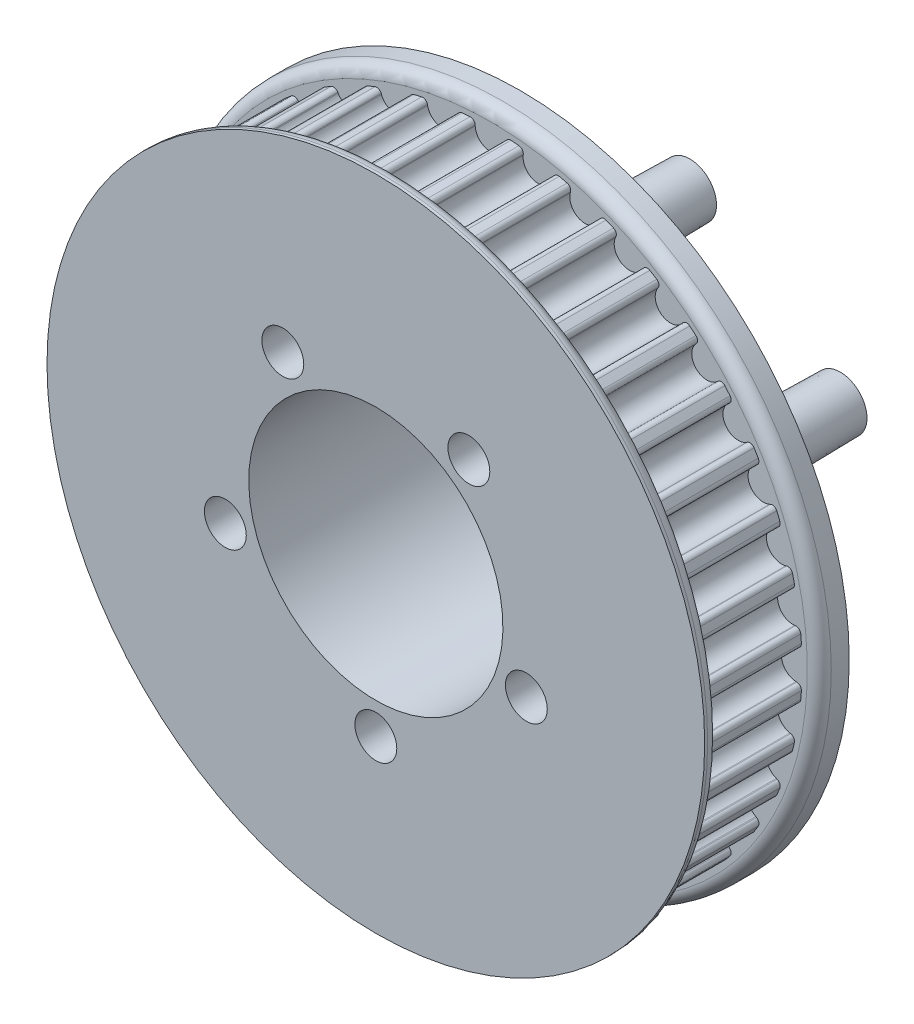
SolidWorks part; units mm, degrees
ref_plane "정면" through (0, 0, 0) normal (0, 0, 1) x (1, 0, 0)
ref_plane "윗면" through (0, 0, 0) normal (0, 1, 0) x (1, 0, 0)
ref_plane "우측면" through (0, 0, 0) normal (1, 0, 0) x (0, 0, -1)
sketch "스케치3" plane through (0, 0, 0) normal (0, 0, 1) x (1, 0, 0)
  line L0 (0, 0) -> (0, 31.2595) construction
  line L1 (0, 0) -> (-4.9795, 31.4391) construction
  line L2 (0, 31.2595) -> (0, 32.9895) construction
  line L3 (-1.5331, 30.6478) -> (-1.5617, 31.2205)
  line L4 (1.5331, 30.6478) -> (1.5617, 31.2205)
  circle A0 centre (0, 0) radius 31.831 construction
  circle A1 centre (0, 0) radius 32.9895 construction
  circle A2 centre (0, 0) radius 31.2595
  circle A3 centre (0, 30.7245) radius 1.535
  dimension "D2" = 63.662
  dimension "D5" = 3.07
  dimension "D3" = 62.519
  dimension "D1" = 9
  dimension "D4" = 2.07
  dimension "D6" = 3.8
extrude "보스-돌출2" add sketch "스케치3" along normal blind 10 contours A2
extrude "컷-돌출2" cut sketch "스케치3<3>" against normal through all and the other way through all contours A3 A2 L3 | A2 A3 | A3 L4 A2 region at (0, 30.3451, 0) region at (-1.5216, 31.0799, 0) region at (1.5216, 31.0799, 0)
sketch "스케치3<3>" plane through (0, 0, 0) normal (0, 0, 1) x (1, 0, 0) same geometry as "스케치3"
fillet "필렛1" radius 0.48 2 edges at (1.5617, 31.2205, 5) (-1.5617, 31.2205, 5)
pattern_circular "원형 패턴1" count 40 over 360 about axis through (0, 0, 10) along (0, 0, -1) of "컷-돌출2", "필렛1"
sketch "스케치8" plane through (0, 0, 10) normal (0, 0, 1) x (1, 0, 0)
  circle A1 centre (0, 0) radius 32.9895 construction
  circle A2 centre (0, 0) radius 32.9895
extrude "보스-돌출3" add sketch "스케치8" along normal blind 1.5
sketch "스케치9" plane through (0, 0, 0) normal (0, 0, -1) x (-1, 0, 0)
  circle A1 centre (0, 0) radius 32.9895 construction
  circle A3 centre (0, 0) radius 32.9895
extrude "보스-돌출4" add sketch "스케치9" along normal blind 3
sketch "스케치7" plane through (0, 0, 0) normal (-1, 0, 0) x (0, 0, 1)
  line L0 (-15.1599, 0) -> (-15.1599, 11)
  line L1 (-15.1599, 0) -> (-1.5048, 0)
  line L3 (-3, 32.9895) -> (-3, -32.9895) construction
  line L5 (-7.7548, 22.06) -> (-7.7548, 0) construction
  line L6 (-1.5048, 0) -> (-1.5048, 34.5)
  line L7 (-0.2048, 26.3473) -> (-5.4, 29.3467)
  line L9 (-7.7548, 22.06) -> (-0.2048, 22.06)
  line L10 (-7.7548, 22.06) -> (-10.6591, 0) construction
  line L13 (-0.2048, 26.3473) -> (-0.2048, 22.06)
  arc A0 (-15.1599, 11) -> (-7.7548, 22.06) centre (-3.198, 11) cw
  arc A1 (-7.7548, 22.06) -> (-1.5048, 34.5) centre (13.2562, 19.2938) cw
  dimension "D1" = 11
  dimension "D2" = 2.4
  dimension "D3" = 6.25
  dimension "D4" = 34.5
  dimension "D5" = 22.06
  dimension "D6" = 7.5
  dimension "D7" = 30
  dimension "D8" = 13.6551
  dimension "D10" = 7.55
  dimension "D11" = 3.8952
revolve "회전2" add sketch "스케치7" angle 360 about L1 region at (0, 10.341, -7.9409) region at (0, 25.0336, -4.3864)
sketch "스케치10" plane through (0, 0, 0) normal (0, 0, 1) x (1, 0, 0)
  line L0 (0, 0) -> (0, 15.875) construction
  circle A0 centre (0, 15.875) radius 2.675
  circle A1 centre (9.3311, 12.8431) radius 2.675 construction
  circle A2 centre (15.098, 4.9056) radius 2.675
  circle A3 centre (15.098, -4.9056) radius 2.675 construction
  circle A4 centre (9.3311, -12.8431) radius 2.675
  circle A5 centre (0, -15.875) radius 2.675 construction
  circle A6 centre (-9.3311, -12.8431) radius 2.675
  circle A7 centre (-15.098, -4.9056) radius 2.675 construction
  circle A8 centre (-15.098, 4.9056) radius 2.675
  circle A9 centre (-9.3311, 12.8431) radius 2.675 construction
  point P25 (0, 0)
  dimension "D1" = 5.35
  dimension "D2" = 15.875
  dimension "D3" = 10
extrude "보스-돌출5" add sketch "스케치10" against normal blind 20
hole_wizard "M5x0.8 탭을 위한 탭 드릴2" positions "스케치14" profile "스케치15" hole size "M5x0.8" standard "Ansi Metric" end condition through all
sketch "스케치14" plane through (0, 0, 11.5) normal (0, 0, -1) x (-1, 0, 0)
  point P26 (-15.098, -4.9056)
  point P28 (0, -15.875)
  point P30 (15.098, -4.9056)
  point P32 (9.3311, 12.8431)
  point P34 (-9.3311, 12.8431)
sketch "스케치15" plane through (15.098, -4.9056, 11.5) normal (1, 0, 0) x (0, -1, 0)
  line L0 (0, 0) -> (0, 31.5)
  line L1 (0, 31.5) -> (2.1, 31.5)
  line L2 (2.1, 31.5) -> (2.1, 0)
  line L5 (2.1, 0) -> (0, 0)
  line L11 (0, -6.35) -> (0, 107.95) construction
  dimension "관통 구멍 지름" = 4.2
  dimension "관통 구멍 깊이" = 31.5
draft "구배1" type of draft neutral plane draft angle 1 faces to draft 5 face at (17.2692, 6.4682, -12.564) face at (11.6645, -11.5352, -13.8692) face at (-6.94, -11.6438, -14.8838) face at (-13.0972, 6.6812, -14.5724) face at (1.7472, 17.9006, -12.9082) neutral plane through (0, 15.875, -20) neutral plane normal (0, 0, -1) parameters "D1"=1
sketch "스케치4" plane through (0, 0, -15.1599) normal (0, 0, -1) x (-1, 0, 0)
  circle A1 centre (0, 0) radius 12.75
  dimension "D1" = 25.5
extrude "컷-돌출3" cut sketch "스케치4" against normal through all
fillet "필렛2" radius 1.2 2 edges at (32.9895, 0, 10) (-32.9895, 0, 0)
equation "\"n\"= 40'number of teeth"
equation "\"D2@스케치3\"=5*\"n\"/(PI)"
equation "\"D1@스케치3\"=360/\"n\""
equation "\"D1@원형 패턴1\"=\"n\""
equation "\"D3@스케치3\"=\"D2@스케치3\"-2*0.225*2.54"
